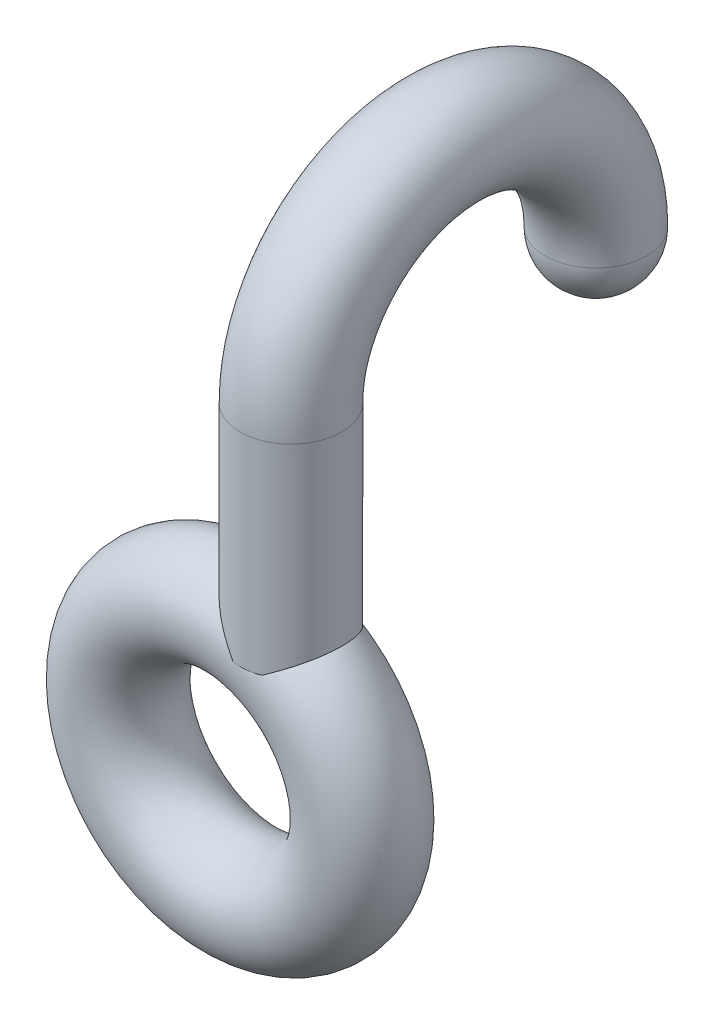
SolidWorks part; units mm, degrees
ref_plane "前视基准面" through (0, 0, 0) normal (0, 0, 1) x (1, 0, 0)
ref_plane "上视基准面" through (0, 0, 0) normal (0, 1, 0) x (1, 0, 0)
ref_plane "右视基准面" through (0, 0, 0) normal (1, 0, 0) x (0, 0, -1)
sketch "草图1" plane through (0, 0, 0) normal (0, 1, 0) x (1, 0, 0)
  line L0 (0, -1000) -> (0, 49000) construction
  line L1 (60, -999.3708) -> (60, 49000.6292) construction
  line L2 (-1000, 0) -> (49000, 0) construction
  circle A0 centre (60, 0) radius 25
  dimension "D2" = 50
  dimension "D1" = 60
revolve "旋转1" add sketch "草图1" angle 360 about L0
ref_plane "基准面1" through (0, 60, 0) normal (0, 1, 0) x (1, 0, 0)
sketch "草图2" plane through (0, 60, 0) normal (0, 1, 0) x (1, 0, 0)
  line L0 (-1000, 0) -> (49000, 0) construction
  line L1 (25, -1000) -> (25, 49000) construction
  circle A0 centre (25, 0) radius 25
  dimension "D2" = 50
  dimension "D1" = 25
extrude "凸台-拉伸1" add sketch "草图2" along normal blind 100
sketch "草图3" plane through (0, 160, 0) normal (0, 1, 0) x (1, 0, 0)
  line L0 (-985.2706, 75) -> (49014.7294, 75) construction
  circle A0 centre (25, 0) radius 25
  circle A1 centre (25, 0) radius 25 construction
  dimension "D1" = 75
revolve "旋转2" add sketch "草图3" angle 180 about L0 reverse direction yes
dome "圆顶1" faces to dome 1 distance 25 reverse direction no elliptical dome no face at (25, 160, -175) parameters "D1"=25
